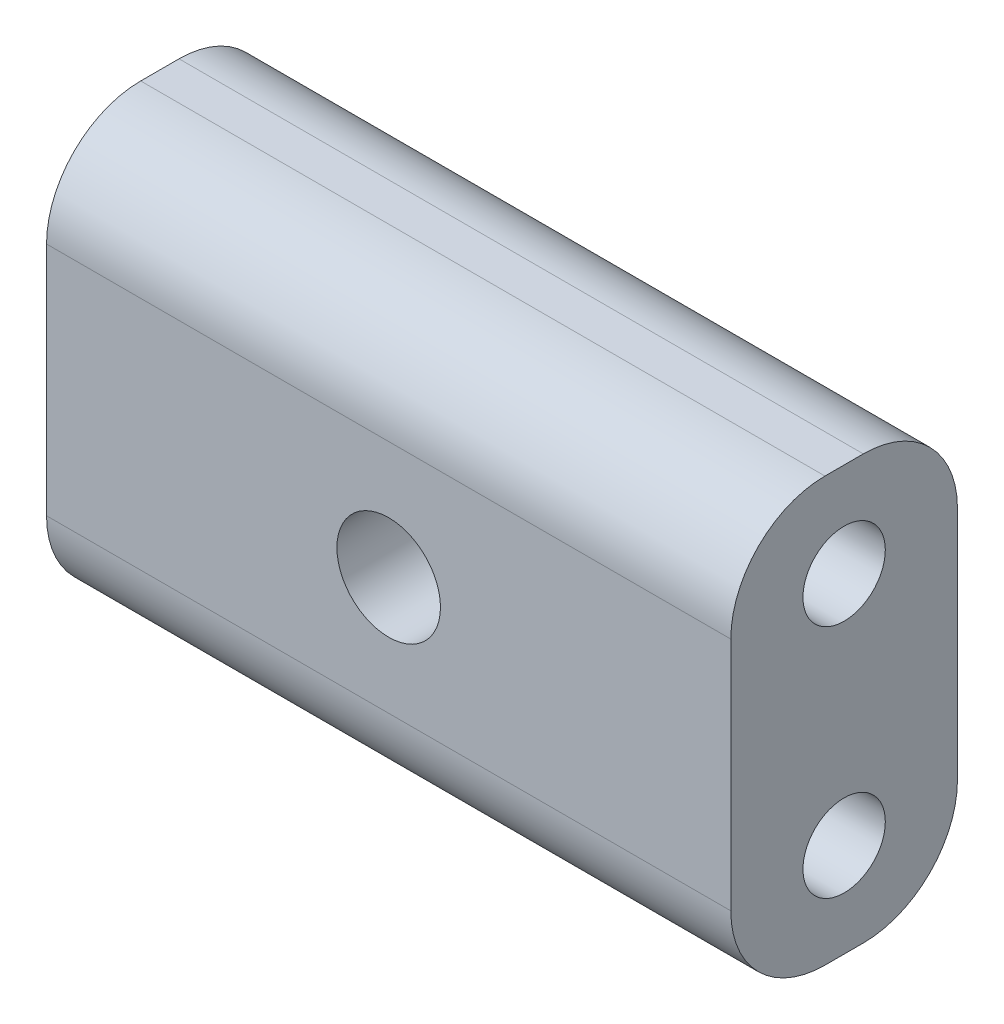
SolidWorks part; units mm, degrees
material "6061 Alloy"
ref_plane "Front Plane" through (0, 0, 0) normal (0, 0, 1) x (1, 0, 0)
ref_plane "Top Plane" through (0, 0, 0) normal (0, 1, 0) x (1, 0, 0)
ref_plane "Right Plane" through (0, 0, 0) normal (1, 0, 0) x (0, 0, -1)
sketch "Sketch1" plane through (0, 0, 0) normal (0, 0, 1) x (1, 0, 0)
  line L1 (-14.5375, 9) -> (14.5375, 9)
  line L2 (-14.5375, 9) -> (-14.5375, -9)
  line L3 (-14.5375, -9) -> (14.5375, -9)
  line L4 (14.5375, 9) -> (14.5375, -9)
  line L5 (0, -9) -> (0, 9) construction
  line L6 (-14.5375, 0) -> (14.5375, 0) construction
  point P0 (0, 0)
  dimension "D1" = 29.075
  dimension "D2" = 18
extrude "3/8" add sketch "Sketch1" along normal blind 9.63
sketch "Sketch2" plane through (-14.5375, 0, 0) normal (-1, 0, 0) x (0, 0, 1)
  line L0 (4.815, 9) -> (4.815, -9) construction
  line L1 (9.63, 9) -> (0, 9) construction
  line L2 (9.63, -9) -> (0, -9) construction
  line L3 (0, 0) -> (9.63, 0) construction
  line L4 (9.63, 9) -> (9.63, -9) construction
  circle A0 centre (4.815, 5) radius 1.75
  circle A1 centre (4.815, -5) radius 1.75
  dimension "D2" = 3.5
  dimension "D1" = 5
extrude "M4_DRILL" cut sketch "Sketch2" against normal blind 8
sketch "Sketch3" plane through (14.5375, 0, 0) normal (1, 0, 0) x (0, 0, -1)
  circle A0 centre (-4.815, -5) radius 1.75 construction
  circle A1 centre (-4.815, 5) radius 1.75 construction
  circle A2 centre (-4.815, -5) radius 1.75
  circle A3 centre (-4.815, 5) radius 1.75
extrude "M4_DRILL2" cut sketch "Sketch3" against normal blind 8
sketch "Sketch5" plane through (0, 0, 0) normal (0, 0, -1) x (-1, 0, 0)
  circle A0 centre (0, 0) radius 2.2
  dimension "D1" = 4.4
extrude "M5_DRILL" cut sketch "Sketch5" against normal up to surface (9.63 mm away) up to face at (0, 0, 9.63)
fillet "Fillet1" radius 4 4 edges at (0, -9, 9.63) (0, -9, 0) (0, 9, 9.63) (0, 9, 0)
